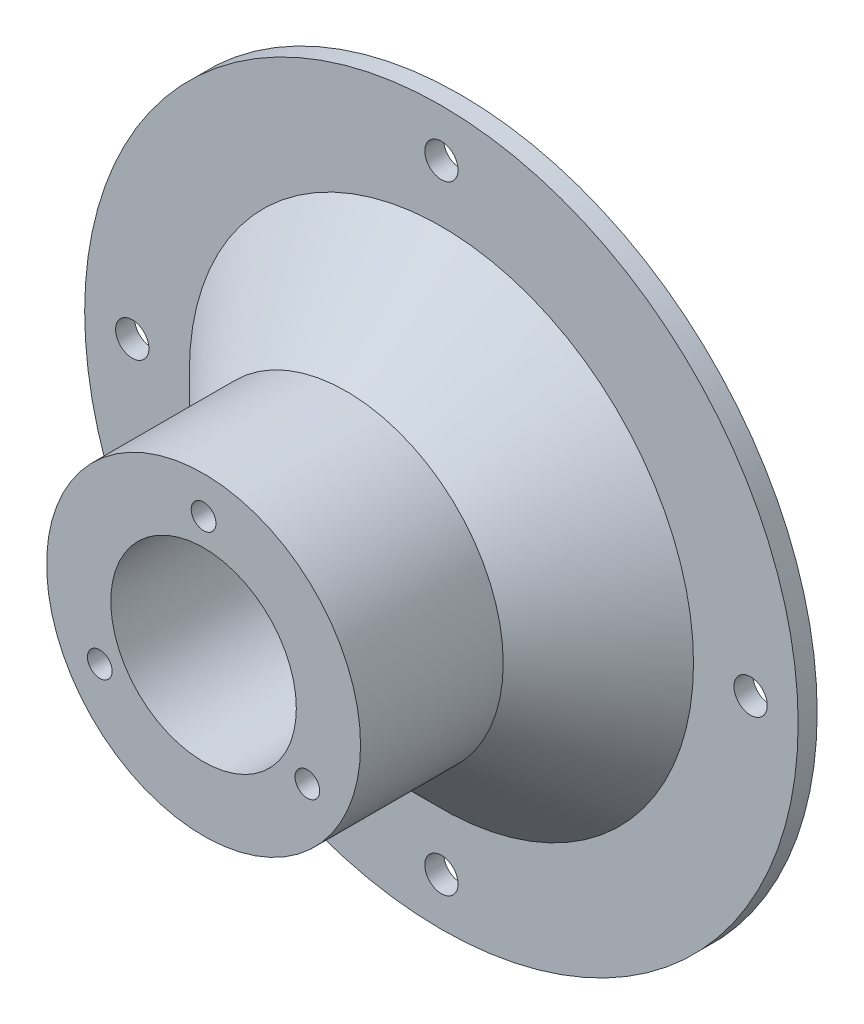
SolidWorks part; units mm, degrees
ref_plane "Спереди" through (0, 0, 0) normal (0, 0, 1) x (1, 0, 0)
ref_plane "Сверху" through (0, 0, 0) normal (0, 1, 0) x (1, 0, 0)
ref_plane "Справа" through (0, 0, 0) normal (1, 0, 0) x (0, 0, -1)
other "Configuration Table"
sketch "Эскиз1" plane through (0, 0, 0) normal (0, 0, 1) x (1, 0, 0)
  circle A0 centre (0, 0) radius 37.5
  dimension "D1" = 75
extrude "Бобышка-Вытянуть1" add sketch "Эскиз1" along normal blind 2
sketch "Эскиз2" plane through (0, 0, 2) normal (0, 0, 1) x (1, 0, 0)
  circle A1 centre (0, 0) radius 32.5 construction
  circle A2 centre (0, 32.5) radius 1.75
  circle A3 centre (32.5, 0) radius 1.75
  circle A4 centre (0, -32.5) radius 1.75
  circle A5 centre (-32.5, 0) radius 1.75
  point P15 (0, 0)
  dimension "D1" = 65
  dimension "D2" = 3.5
  dimension "D3" = 4
extrude "Вырез-Вытянуть1" cut sketch "Эскиз2" against normal up to surface (2 mm away) up to face at (37.5, 0, 0)
sketch "Эскиз3" plane through (0, 0, 2) normal (0, 0, 1) x (1, 0, 0)
  circle A0 centre (0, 0) radius 16.5
  dimension "D1" = 33
extrude "Бобышка-Вытянуть2" add sketch "Эскиз3" along normal blind 25
sketch "Эскиз4" plane through (0, 0, 27) normal (0, 0, 1) x (1, 0, 0)
  circle A0 centre (0, 0) radius 9.75
  circle A1 centre (0, 0) radius 12.6 construction
  circle A2 centre (0, 12.6) radius 1.3
  circle A3 centre (10.9119, -6.3) radius 1.3
  circle A4 centre (-10.9119, -6.3) radius 1.3
  point P12 (0, 0)
  dimension "D1" = 19.5
  dimension "D2" = 2.6
  dimension "D3" = 25.2
  dimension "D4" = 3
extrude "Вырез-Вытянуть2" cut sketch "Эскиз4" against normal up to surface (27 mm away) up to face at (1.75, 32.5, 0)
chamfer "Фаска1" distance 10 angle 45 1 edges at (16.5, 0, 2)
